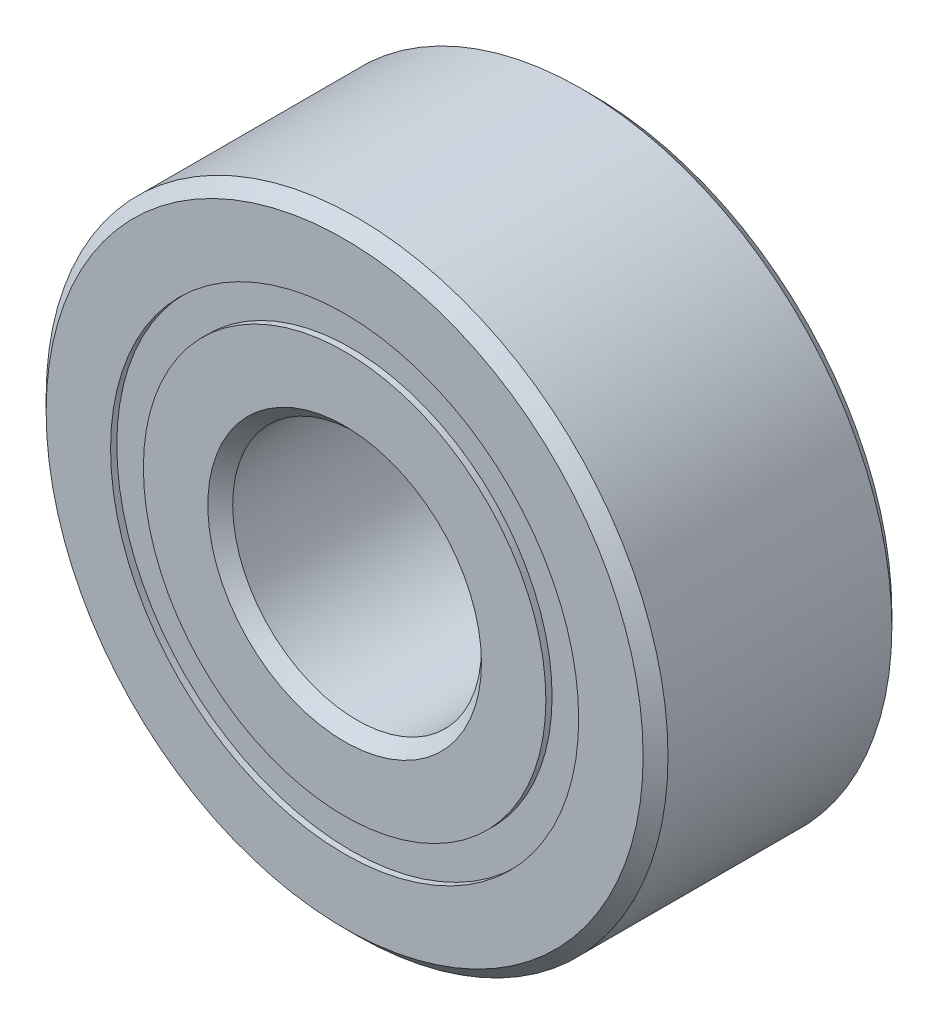
SolidWorks part; units mm, degrees
ref_plane "Front Plane" through (0, 0, 0) normal (0, 0, 1) x (1, 0, 0)
ref_plane "Top Plane" through (0, 0, 0) normal (0, 1, 0) x (1, 0, 0)
ref_plane "Right Plane" through (0, 0, 0) normal (1, 0, 0) x (0, 0, -1)
sketch "Sketch1" plane through (0, 0, 0) normal (1, 0, 0) x (0, 0, -1)
  line L0 (-2, 0) -> (2, 0) construction
  line L1 (0, 5) -> (0, -5) construction
  line L2 (1.8, 5) -> (-1.8, 5)
  line L3 (-1.8, 5) -> (-2, 4.8)
  line L4 (-2, 4.8) -> (-2, 3.7637)
  line L5 (-2, 3.7637) -> (-0.8889, 3.7637)
  line L6 (2, 3.7637) -> (0.8889, 3.7637)
  line L7 (2, 4.8) -> (2, 3.7637)
  line L8 (1.8, 5) -> (2, 4.8)
  line L9 (0, 5) -> (0, 3.5) construction
  line L10 (0, 3.5) -> (0, 2) construction
  arc A0 (-0.8889, 3.7637) -> (0.8889, 3.7637) centre (0, 3.5) cw
  point P14 (0, 2)
  dimension "Width" = 4
  dimension "OD" = 10
  dimension "D1" = 45
  dimension "D2" = 0.2
  dimension "Shaft Dia" = 4
  dimension "D3" = 1.7778
  dimension "D4" = 0.2637
revolve "Revolve1" add sketch "Sketch1" angle 360 about L0
sketch "Sketch3" plane through (0, 0, 0) normal (1, 0, 0) x (0, 0, -1)
  line L0 (-2, 3.2363) -> (-0.8889, 3.2363)
  line L1 (0, 5) -> (0, -5) construction
  line L2 (-2, 4.8) -> (-2, 3.7637) construction
  line L3 (-2, 3.2363) -> (-2, 2.2)
  line L4 (-1.8, 5) -> (-2, 4.8) construction
  line L5 (-2, 2.2) -> (-1.8, 2)
  line L6 (-1.8, 2) -> (1.8, 2)
  line L7 (1.8, 5) -> (1.8, -5) construction
  line L8 (1.8, 2) -> (2, 2.2)
  line L9 (2, -4.8) -> (2, 4.8) construction
  line L10 (2, 2.2) -> (2, 3.2363)
  line L11 (2, 3.2363) -> (0.8889, 3.2363)
  line L13 (1.8, 5) -> (2, 4.8) construction
  arc A0 (0.8889, 3.7637) -> (-0.8889, 3.7637) centre (0, 3.5) ccw construction
  arc A1 (0.8889, 3.2363) -> (-0.8889, 3.2363) centre (0, 3.5) cw
revolve "Revolve3" add sketch "Sketch3" angle 360 about L0
sketch "Sketch4" plane through (0, 0, 0) normal (1, 0, 0) x (0, 0, -1)
  line L0 (-0.9272, 3.5) -> (0.9272, 3.5)
  arc A2 (-0.9272, 3.5) -> (0.9272, 3.5) centre (0, 3.5) cw
  arc A3 (0.8889, 3.7637) -> (-0.8889, 3.7637) centre (0, 3.5) ccw construction
revolve "Revolve4" add sketch "Sketch4" angle 360 about L0
ref_axis "Axis1" through (0, 0, -2) along (0, 0, 1)
pattern_circular "CirPattern1" count 12 every 30 about axis through (0, 0, -2) along (0, 0, 1) of bodies 104
sketch "Sketch5" plane through (0, 0, 0) normal (1, 0, 0) x (0, 0, -1)
  line L0 (-2, 3.7637) -> (-0.8889, 3.7637) construction
  line L1 (-1.9, 3.7637) -> (-0.9272, 3.7637)
  line L2 (-1.9, 3.7637) -> (-1.9, 3.2363)
  line L3 (-1.9, 3.2363) -> (-0.9272, 3.2363)
  line L4 (-0.9272, 3.7637) -> (-0.9272, 3.2363)
  line L5 (-2, 3.2363) -> (-0.8889, 3.2363) construction
  line L6 (2, 3.7637) -> (0.8889, 3.7637) construction
  line L7 (1.9, 3.7637) -> (0.9272, 3.7637)
  line L8 (1.9, 3.7637) -> (1.9, 3.2363)
  line L9 (1.9, 3.2363) -> (0.9272, 3.2363)
  line L10 (0.9272, 3.7637) -> (0.9272, 3.2363)
  line L11 (2, 3.2363) -> (0.8889, 3.2363) construction
  line L12 (-1.8, 5) -> (-2, 4.8) construction
  point P18 (-1.9, 4.9)
revolve "Revolve5" add sketch "Sketch5" angle 360 about L0
sketch "Sketch6" plane through (0, 0, 0) normal (1, 0, 0) x (0, 0, -1)
  line L0 (2, 0) -> (-2, 0) construction
  line L1 (2, 3.7637) -> (1.2126, 3.7637)
  line L2 (2, 3.7637) -> (2, 6.9469)
  line L3 (2, 6.9469) -> (1.2126, 6.9469)
  line L4 (1.2126, 3.7637) -> (1.2126, 6.9469)
  dimension "Th" = 0.7874
  dimension "Flange OD" = 13.8938
revolve "Revolve6" [suppressed] add sketch "Sketch6" angle 360 about L0
equation "\"D2@Sketch1\" = \"Width@Sketch1\"*.05"
equation "\"D3@Sketch1\" = \"Width@Sketch1\"/2.25"
equation "\"D4@Sketch1\" = (((\"OD@Sketch1\"-\"Width@Sketch1\")/2)/3.25)/3.5"
equation "\"D2@CirPattern1\" = 360/\"Balls@CirPattern1\""
